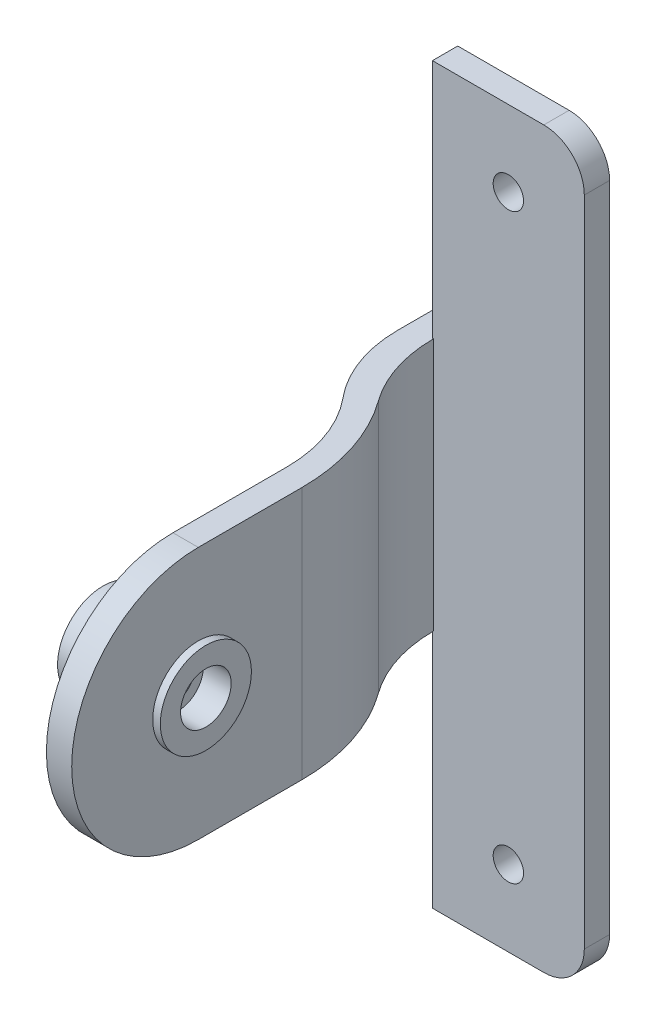
SolidWorks part; units mm, degrees
ref_plane "Front Plane" through (0, 0, 0) normal (0, 0, 1) x (1, 0, 0)
ref_plane "Top Plane" through (0, 0, 0) normal (0, 1, 0) x (1, 0, 0)
ref_plane "Right Plane" through (0, 0, 0) normal (1, 0, 0) x (0, 0, -1)
sketch "Sketch1" plane through (0, 0, 0) normal (1, 0, 0) x (0, 0, -1)
  line L1 (0, 12.5) -> (34.45, 12.5)
  line L2 (0, 1.5) -> (0, -12.5)
  line L3 (0, -12.5) -> (34.45, -12.5)
  line L4 (34.45, 12.5) -> (34.45, -12.5)
  circle A0 centre (0, 0) radius 1.5
  circle A1 centre (0, 0) radius 12.5 construction
  arc A2 (0, 12.5) -> (0, -12.5) centre (0, 0) ccw
  dimension "D1" = 3
  dimension "D2" = 25
  dimension "D3" = 34.45
extrude "Boss-Extrude1" add sketch "Sketch1" along normal blind 2.5 contours L1 A2 A0 L3 L4 region at (0, 0, -12.3069)
sketch "Sketch2" plane through (0, 0, 0) normal (-1, 0, 0) x (0, 0, 1)
  circle A0 centre (0, 0) radius 1.5
  circle A1 centre (0, 0) radius 4.5
  dimension "D1" = 9
  dimension "D2" = 3
extrude "Boss-Extrude2" add sketch "Sketch2" along normal blind 6.9 and the other way offset from surface 0.75 other way up to face at (2.5, 0, -14.1)
sketch "Sketch4" plane through (2.5, 0, 0) normal (1, 0, 0) x (0, 0, -1)
  circle A0 centre (0, 0) radius 2.5
extrude "Cut-Extrude1" cut sketch "Sketch4" against normal blind 2
sketch "Sketch5" plane through (2.5, 0, 0) normal (1, 0, 0) x (0, 0, -1)
  circle A0 centre (0, 0) radius 4.5
  circle A1 centre (0, 0) radius 2.5
  dimension "D1" = 9
  dimension "D2" = 5
extrude "Boss-Extrude3" add sketch "Sketch5" along normal blind 0.75
sketch "Sketch6" plane through (0, 0, -34.45) normal (0, 0, -1) x (-1, 0, 0)
  line L1 (-8.8125, 36.25) -> (53.3216, 36.25)
  line L3 (6.25, -36.25) -> (53.3216, -36.25)
  line L4 (53.3216, 36.25) -> (53.3216, -36.25)
  line L6 (53.3216, -36.25) -> (-19.1784, 36.25) construction
  line L7 (6.25, -36.25) -> (-19.1784, -36.25)
  line L9 (-8.8125, 36.25) -> (-19.1784, 36.25)
  line L10 (-19.1784, -36.25) -> (-19.1784, 36.25)
  line L11 (53.3216, 36.25) -> (-19.1784, -36.25) construction
  point P4 (17.0716, 0)
  dimension "D1" = 72.5
  dimension "D2" = 72.5
extrude "Boss-Extrude4" add sketch "Sketch6" against normal blind 2.5
ref_plane "Plane1" through (-17.0716, 0, 0) normal (1, 0, 0) x (0, 0, -1)
ref_plane "Plane2" through (9.4784, 0, 0) normal (1, 0, 0) x (0, 0, -1)
sketch "Sketch7" plane through (0, 0, -31.95) normal (0, 0, 1) x (1, 0, 0)
  line L7 (1.7881, -3.3824) -> (-5.2119, -3.3824)
  line L12 (1.7881, -3.3824) -> (1.7881, -19.8824)
  line L18 (1.7881, -19.8824) -> (-5.2119, -19.8824)
  line L19 (-5.2119, -3.3824) -> (-5.2119, -19.8824)
  line L20 (1.7881, -3.3824) -> (-5.2119, -19.8824) construction
  line L21 (1.7881, -19.8824) -> (-5.2119, -3.3824) construction
  line L22 (-24.5, -4) -> (-8.5, -4)
  line L23 (-24.5, -4) -> (-24.5, 4)
  line L24 (-24.5, 4) -> (-8.5, 4)
  line L25 (-8.5, -4) -> (-8.5, 4)
  line L26 (-24.5, -4) -> (-8.5, 4) construction
  line L27 (-24.5, 4) -> (-8.5, -4) construction
  point P0 (-16.5, 0)
  point P2 (-1.7119, -11.6324)
  dimension "D1" = 16
  dimension "D2" = 16.5
  dimension "D3" = 7
  dimension "D4" = 8
extrude "Cut-Extrude2" cut sketch "Sketch7" against normal up to next
sketch "Sketch8" plane through (0, 0, 0) normal (0, 1, 0) x (1, 0, 0)
  line L13 (0, 7.7296) -> (2.5, 7.7296)
  line L17 (0, 11.2296) -> (0, 7.7296)
  line L18 (-3.7212, 31.95) -> (-3.7212, 29.45)
  line L19 (-6.2212, 31.95) -> (-6.2212, 28.45)
  line L20 (-6.2212, 31.95) -> (-3.7212, 31.95)
  line L22 (2.5, 7.7296) -> (2.5, 10.2296)
  line L23 (2.5, 0) -> (2.5, 31.95) construction
  line L24 (0, 0) -> (0, 31.95) construction
  line L25 (0, -13.75) -> (0, 13.75) construction
  line L26 (-53.3216, 31.95) -> (19.1784, 31.95) construction
  line L27 (19.1784, 31.95) -> (19.1784, 34.45) construction
  arc A5 (-1.1155, 21.3996) -> (2.5, 10.2296) centre (-16.5626, 10.2296) cw
  arc A6 (-3.1485, 19.9446) -> (-6.2212, 28.45) centre (7.0867, 28.45) cw
  arc A7 (-3.1485, 19.9446) -> (0, 11.2296) centre (-13.636, 11.2296) cw
  arc A8 (-3.7212, 29.45) -> (-1.1155, 21.3996) centre (10.0176, 29.45) ccw
  point P0 (2.5, 7.7296)
  dimension "D3" = 22.8996
  dimension "D4" = 3.5
  dimension "D1" = 2.5
  dimension "D2" = 2.5
  dimension "D5" = 3.5
  dimension "D6" = 2.5
  dimension "D7" = 2.5
sketch "Sketch9" plane through (0, -12.5, 0) normal (0, -1, 0) x (1, 0, 0)
  line L0 (2.5, 0) -> (2.5, -31.95) construction
  line L1 (0, -31.95) -> (2.5, -31.95)
  line L2 (0, -31.95) -> (0, -9.5612)
  line L3 (0, -9.5612) -> (2.5, -9.5612)
  line L4 (2.5, -31.95) -> (2.5, -9.5612)
extrude "Cut-Extrude3" cut sketch "Sketch9" against normal up to next
extrude "Boss-Extrude5" add sketch "Sketch8" along normal mid plane 25
fillet "Fillet1" [suppressed] radius 4
fillet "Fillet2" radius 1 8 edges at (-5.2119, -3.3824, -33.2) (-5.2119, -19.8824, -33.2) (1.7881, -3.3824, -33.2) (-8.5, 4, -33.2) (1.7881, -19.8824, -33.2) (-8.5, -4, -33.2) (-24.5, 4, -33.2) (-24.5, -4, -33.2)
fillet "Fillet3" radius 4 4 edges at (19.1784, -36.25, -33.2) (19.1784, 36.25, -33.2) (-53.3216, 36.25, -33.2) (-53.3216, -36.25, -33.2)
sketch "Sketch10" plane through (0, 0, 0) normal (0, 1, 0) x (1, 0, 0)
  line L0 (15.1784, 31.95) -> (19.1784, 31.95) construction
  line L1 (21.7259, 31.95) -> (-56.5098, 31.95)
  line L2 (21.7259, 31.95) -> (21.7259, 38.24)
  line L3 (21.7259, 38.24) -> (-56.5098, 38.24)
  line L4 (-56.5098, 31.95) -> (-56.5098, 38.24)
  point P6 (-56.5098, 40.0909)
  point P7 (21.7259, 38.24)
extrude "Cut-Extrude4" cut sketch "Sketch10" against normal through all both and the other way through all
sketch "Sketch11" plane through (0, 0, 0) normal (0, 1, 0) x (1, 0, 0)
  line L0 (-3.7212, 29.45) -> (-3.7212, 31.95) construction
  line L1 (11.1788, 31.95) -> (-3.7212, 31.95)
  line L2 (11.1788, 31.95) -> (11.1788, 29.45)
  line L3 (11.1788, 29.45) -> (-3.7212, 29.45)
  line L4 (-3.7212, 31.95) -> (-3.7212, 29.45)
  line L5 (-3.7212, 31.95) -> (-6.2212, 31.95) construction
  point P5 (0, 0)
  point P6 (0, 0)
  point P7 (0, 0)
  point P8 (-9.2644, 31.9699)
  point P9 (-8.7012, 31.95)
  point P11 (0, 0)
  point P12 (-6.2012, 31.95)
  dimension "D1" = 2.5
  dimension "D2" = 14.9
extrude "Boss-Extrude6" add sketch "Sketch11" along normal mid plane 25
sketch "Sketch12" plane through (0, 0, -31.95) normal (0, 0, -1) x (-1, 0, 0)
  line L0 (24.4475, 0) -> (-24.4475, 0) construction
  line L1 (-11.1788, 36.25) -> (61.3212, 36.25) construction
  line L2 (-11.1788, 36.25) -> (-11.1788, -36.25) construction
  line L3 (-11.1788, -36.25) -> (61.3212, -36.25) construction
  line L4 (61.3212, 36.25) -> (61.3212, -36.25) construction
  line L5 (-11.1788, 36.25) -> (61.3212, -36.25) construction
  line L6 (61.3212, 36.25) -> (-11.1788, -36.25) construction
  line L7 (-11.1788, 12.5) -> (-11.1788, -12.5) construction
  circle A0 centre (-3.6788, 28.75) radius 1.5
  circle A1 centre (-3.6788, -28.75) radius 1.5
  circle A2 centre (-3.6788, 28.75) radius 3
  circle A3 centre (-3.6788, -28.75) radius 3
  point P4 (-11.1788, 0)
  point P13 (-11.1788, 36.25)
  dimension "D3" = 3
  dimension "D5" = 6
  dimension "D1" = 72.5
  dimension "D2" = 72.5
  dimension "D4" = 7.5
sketch "Sketch13" plane through (0, 0, -31.95) normal (0, 0, -1) x (-1, 0, 0)
  line L1 (-11.1788, 12.5) -> (3.8212, 12.5)
  line L2 (-11.1788, 12.5) -> (-11.1788, 28.75)
  line L4 (3.8212, 12.5) -> (3.8212, 28.75)
  line L5 (-3.6788, 36.25) -> (-7.1788, 36.25)
  line L6 (-11.1788, 32.25) -> (-11.1788, 28.75)
  line L7 (3.8212, 28.75) -> (3.8212, 36.25)
  line L8 (3.8212, 36.25) -> (-3.6788, 36.25)
  arc A1 (-7.1788, 36.25) -> (-11.1788, 32.25) centre (-7.1788, 32.25) ccw
  dimension "D2" = 4
  dimension "D1" = 7.5
extrude "Boss-Extrude7" add sketch "Sketch13" against normal blind 2.5
mirror "Mirror1" about plane through (0, 0, 0) normal (0, 1, 0) of "Boss-Extrude6", "Boss-Extrude7"
sketch "Sketch14" plane through (0, 0, -31.95) normal (0, 0, -1) x (-1, 0, 0)
  line L0 (3.8212, 36.25) -> (-7.1788, 36.25) construction
  line L1 (3.8212, 12.5) -> (3.8212, 36.25) construction
  circle A0 centre (-3.6788, 28.75) radius 1.5
  point P3 (0, 0)
  dimension "D1" = 7.5
  dimension "D2" = 7.5
extrude "Cut-Extrude5" cut sketch "Sketch14" against normal blind 2.5
sketch "Sketch15" plane through (0, 0, -31.95) normal (0, 0, -1) x (-1, 0, 0)
  circle A0 centre (-3.6788, 28.75) radius 2.5
  circle A1 centre (-3.6788, 28.75) radius 4
  dimension "D1" = 8
  dimension "D2" = 5
extrude "Boss-Extrude8" [suppressed] add sketch "Sketch15" against normal blind 6
mirror "Mirror2" about plane through (0, 0, 0) normal (0, 1, 0) of "Cut-Extrude5", "Boss-Extrude8"
